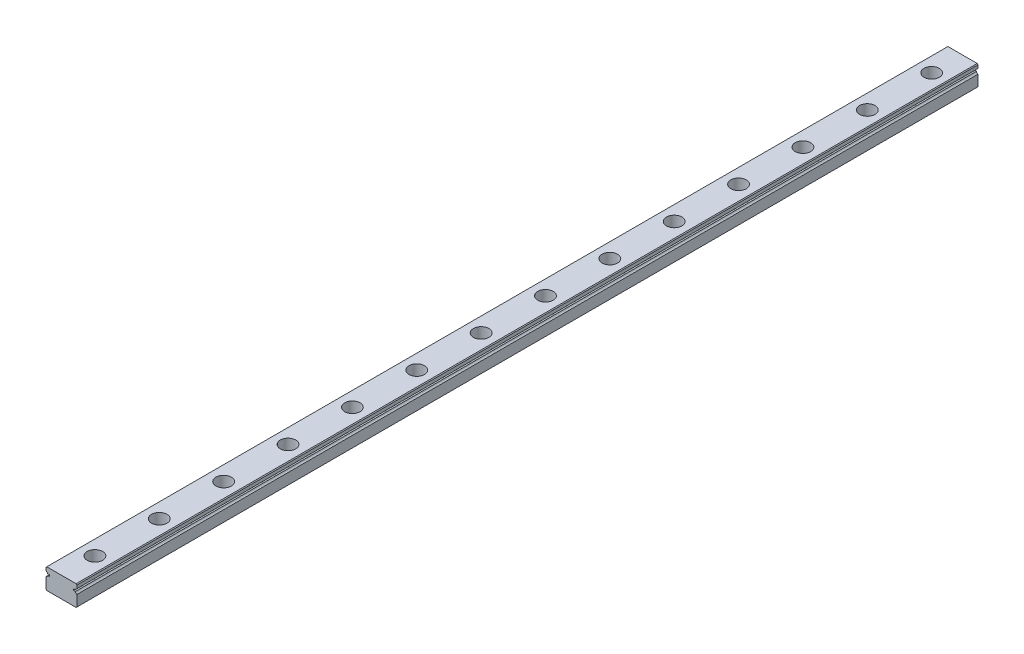
SolidWorks part; units mm, degrees
ref_plane "Спереди" through (0, 0, 0) normal (0, 0, 1) x (1, 0, 0)
ref_plane "Сверху" through (0, 0, 0) normal (0, 1, 0) x (1, 0, 0)
ref_plane "Справа" through (0, 0, 0) normal (1, 0, 0) x (0, 0, -1)
sketch "Эскиз1" plane through (0, 0, 0) normal (0, 0, 1) x (1, 0, 0)
  line L0 (-6, 3.7) -> (-5.7, 4)
  line L1 (-5.7, -4) -> (5.7, -4)
  line L2 (-6, -3.7) -> (-6, 0.549)
  line L3 (-5.7, 4) -> (5.7, 4)
  line L4 (6, -3.7) -> (6, 0.549)
  line L5 (-6, -4) -> (6, 4) construction
  line L6 (-6, 4) -> (6, -4) construction
  line L7 (-6, -3.7) -> (-5.7, -4)
  line L8 (5.7, -4) -> (6, -3.7)
  line L9 (5.7, 4) -> (6, 3.7)
  line L10 (-6, 2.451) -> (-6, 3.7)
  line L11 (-5.3546, 1.7981) -> (-4.6435, 1.7981)
  line L12 (0, 5.4188) -> (0, -5.747) construction
  line L13 (-5.3546, 1.2019) -> (-4.6435, 1.2019)
  line L14 (-4.6435, 1.7981) -> (-4.6435, 1.2019)
  line L15 (4.6435, 1.7981) -> (4.6435, 1.2019)
  line L16 (5.3546, 1.2019) -> (4.6435, 1.2019)
  line L17 (5.3546, 1.7981) -> (4.6435, 1.7981)
  line L18 (6, 2.451) -> (6, 3.7)
  line L19 (4.6435, 1.7981) -> (5.3546, 1.7981) construction
  arc A0 (-6, 0.549) -> (-5.3546, 1.2019) centre (-6.3091, 1.5) ccw
  arc A1 (-5.3546, 1.7981) -> (-6, 2.451) centre (-6.3091, 1.5) ccw
  arc A2 (5.3546, 1.7981) -> (6, 2.451) centre (6.3091, 1.5) cw
  arc A3 (6, 0.549) -> (5.3546, 1.2019) centre (6.3091, 1.5) cw
  point P0 (0, 0)
extrude "Бобышка-Вытянуть1" add sketch "Эскиз1" along normal blind 350
sketch "Эскиз2" plane through (0, 4, 0) normal (0, 1, 0) x (1, 0, 0)
  line L0 (0, 0) -> (0, -26.2396) construction
  line L1 (5.7, 0) -> (-5.7, 0) construction
  line L2 (-3.8306, -12) -> (3.8306, -12) construction
  circle A0 centre (0, -12) radius 3
  circle A1 centre (0, -12) radius 1.75
  dimension "D2" = 3.5
  dimension "D3" = 6
  dimension "D1" = 12
extrude "Вырез-Вытянуть1" cut sketch "Эскиз2" against normal blind 4.5
extrude "Вырез-Вытянуть2" cut sketch "Эскиз2<2>" against normal through all contours A1 region at (0, 4, 12)
sketch "Эскиз2<2>" plane through (0, 4, 0) normal (0, 1, 0) x (1, 0, 0) same geometry as "Эскиз2"
pattern_linear "Линейный массив1" count 16 spacing 25 along (0, 0, 1) of "Вырез-Вытянуть1", "Вырез-Вытянуть2"
